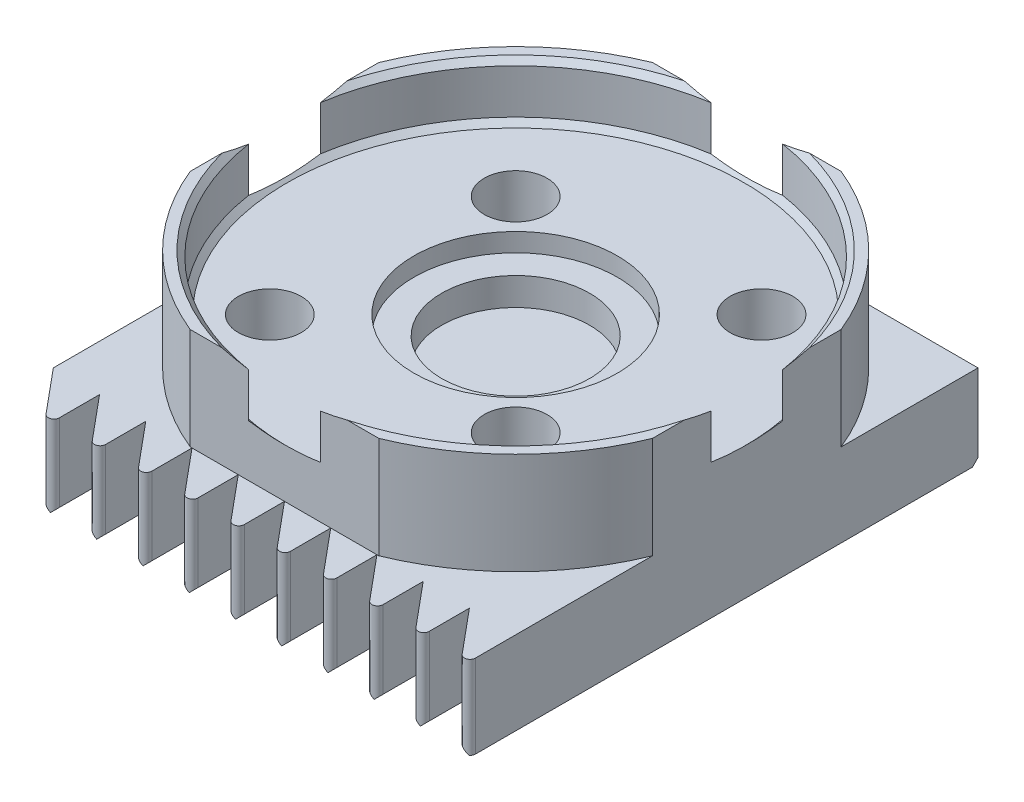
SolidWorks part; units mm, degrees
ref_plane "Front Plane" through (0, 0, 0) normal (0, 0, 1) x (1, 0, 0)
ref_plane "Top Plane" through (0, 0, 0) normal (0, 1, 0) x (1, 0, 0)
ref_plane "Right Plane" through (0, 0, 0) normal (1, 0, 0) x (0, 0, -1)
sketch "Sketch1" plane through (0, 0, 0) normal (0, 1, 0) x (1, 0, 0)
  line L0 (-6.6468, -6.6468) -> (6.6468, 6.6468) construction
  line L1 (-5.5331, 5.5331) -> (5.5331, -5.5331) construction
  line L2 (0, 0) -> (0, 3.1277) construction
  circle A0 centre (0, 0) radius 13.5
  circle A1 centre (0, 0) radius 5.5
  circle A2 centre (0, 0) radius 7.825 construction
  circle A3 centre (-5.5331, 5.5331) radius 1.7
  circle A4 centre (5.5331, -5.5331) radius 1.7
  circle A5 centre (0, 0) radius 9.4 construction
  circle A6 centre (-6.6468, -6.6468) radius 1.7
  circle A7 centre (6.6468, 6.6468) radius 1.7
  dimension "D1" = 27
  dimension "D2" = 11
  dimension "D3" = 15.65
  dimension "D4" = 18.8
  dimension "D5" = 3.4
  dimension "D6" = 45
extrude "Boss-Extrude1" add sketch "Sketch1" along normal blind 2.5 contours A0 A7 A6 A4 A3 A1 region at (-13.1182, 0, 0)
sketch "Sketch2" plane through (0, 2.5, 0) normal (0, 1, 0) x (1, 0, 0)
  circle A0 centre (0, 0) radius 12.65
  circle M6 centre (0, 0) radius 13.5
extrude "Boss-Extrude2" add sketch "Sketch2" along normal blind 3 contours A0 M6 region at (-13.1182, 2.5, 0)
sketch "Sketch3" plane through (0, 0, 0) normal (0, -1, 0) x (1, 0, 0)
  line L1 (12.5, -12.5) -> (-12.5, -12.5)
  line L2 (12.5, -12.5) -> (12.5, 12.5)
  line L3 (12.5, 12.5) -> (-12.5, 12.5)
  line L4 (-12.5, -12.5) -> (-12.5, 12.5)
  line L5 (12.5, -12.5) -> (-12.5, 12.5) construction
  line L6 (12.5, 12.5) -> (-12.5, -12.5) construction
  circle A0 centre (-5.5331, -5.5331) radius 1.7 construction
  circle A1 centre (6.6468, -6.6468) radius 1.7 construction
  circle A2 centre (5.5331, 5.5331) radius 1.7 construction
  circle A3 centre (-6.6468, 6.6468) radius 1.7 construction
  circle A4 centre (-5.5331, -5.5331) radius 1.7 construction
  circle A5 centre (6.6468, -6.6468) radius 1.7 construction
  circle A6 centre (5.5331, 5.5331) radius 1.7 construction
  circle A7 centre (-6.6468, 6.6468) radius 1.7 construction
  circle A8 centre (-6.6468, 6.6468) radius 3
  circle A9 centre (5.5331, 5.5331) radius 3
  circle A10 centre (6.6468, -6.6468) radius 3
  circle A11 centre (-5.5331, -5.5331) radius 3
  point P0 (0, 0)
  circle M5 centre (0, 0) radius 5.5
  circle M6 centre (0, 0) radius 13.5
  dimension "D1" = 6
  dimension "D2" = 25
extrude "Boss-Extrude3" add sketch "Sketch3" along normal blind 4.5 contours L4 L1 L2 L3 A11 A9 A10 A8 M6 M5 | L4 L3 M6 | L4 L1 M6 | L1 L2 M6 | L2 L3 M6 | A11 A9 M5 region at (10.3804, 0, -10.3804) region at (0, 0, -12.1464) region at (-10.3804, 0, -10.3804) region at (10.3804, 0, 10.3804) region at (-10.3804, 0, 10.3804) region at (0, 0, 0)
chamfer "Chamfer2" distance 0.3 angle 45 1 edges at (0, 2.5, 12.65)
sketch "Sketch4" plane through (0, 0, 0) normal (0, 1, 0) x (1, 0, 0)
  circle A0 centre (0, 0) radius 5.5 construction
  circle A1 centre (0, 0) radius 5.5
  circle A2 centre (0, 0) radius 4
  arc M1 (2.6146, -4.8388) -> (4.8388, -2.6146) centre (5.5331, -5.5331) cw
  arc M2 (4.8388, -2.6146) -> (-2.6146, 4.8388) centre (0, 0) ccw
  arc M3 (-2.6146, 4.8388) -> (-4.8388, 2.6146) centre (-5.5331, 5.5331) cw
  arc M4 (-4.8388, 2.6146) -> (2.6146, -4.8388) centre (0, 0) ccw
  dimension "D1" = 8
extrude "Boss-Extrude4" add sketch "Sketch4" along normal blind 1.5 contours A2 M4 M1 M2 M3 | A1 M3 | A1 M1 region at (5.1813, 0, 1.3103) region at (-3.6647, 0, -3.6647) region at (3.6647, 0, 3.6647)
sketch "Sketch6" plane through (0, 0, 0) normal (0, -1, 0) x (1, 0, 0)
  line L0 (5.099, -12.5) -> (-5.099, -12.5) construction
  line L1 (12.5, 5.099) -> (12.5, -5.099) construction
  line L2 (-5.099, 12.5) -> (5.099, 12.5) construction
  line L3 (-12.5, -5.099) -> (-12.5, 5.099) construction
  line L4 (5.099, -12.5) -> (-5.099, -12.5)
  line L5 (12.5, 5.099) -> (12.5, -5.099)
  line L6 (-5.099, 12.5) -> (5.099, 12.5)
  line L7 (-12.5, -5.099) -> (-12.5, 5.099)
  arc A0 (-5.099, -12.5) -> (5.099, -12.5) centre (0, 0) ccw construction
  arc A1 (12.5, -5.099) -> (12.5, 5.099) centre (0, 0) ccw construction
  arc A2 (5.099, 12.5) -> (-5.099, 12.5) centre (0, 0) ccw construction
  arc A3 (-12.5, 5.099) -> (-12.5, -5.099) centre (0, 0) ccw construction
  arc A4 (-5.099, -12.5) -> (5.099, -12.5) centre (0, 0) ccw
  arc A5 (12.5, -5.099) -> (12.5, 5.099) centre (0, 0) ccw
  arc A6 (5.099, 12.5) -> (-5.099, 12.5) centre (0, 0) ccw
  arc A7 (-12.5, 5.099) -> (-12.5, -5.099) centre (0, 0) ccw
extrude "Cut-Extrude1" cut sketch "Sketch6" against normal through all
chamfer "Chamfer3" distance 0.3 angle 45 4 edges at (8.9449, 5.5, -8.9449) (-8.9449, 5.5, -8.9449) (-8.9449, 5.5, 8.9449) (8.9449, 5.5, 8.9449)
sketch "Sketch7" plane through (0, -4.5, 0) normal (0, -1, 0) x (1, 0, 0)
  line L0 (12.5, 12.5) -> (-12.5, 12.5) construction
  line L1 (12.5, 12.5) -> (-12.5, 12.5)
  line L2 (-12.5, 12.5) -> (-10, 15.5)
  line L3 (-10, 15.5) -> (-10, 12.5)
  line L4 (-7.5, 15.5) -> (-7.5, 12.5)
  line L5 (-10, 12.5) -> (-7.5, 15.5)
  line L6 (-5, 15.5) -> (-5, 12.5)
  line L7 (-7.5, 12.5) -> (-5, 15.5)
  line L8 (-2.5, 15.5) -> (-2.5, 12.5)
  line L9 (-5, 12.5) -> (-2.5, 15.5)
  line L10 (0, 15.5) -> (0, 12.5)
  line L11 (-2.5, 12.5) -> (0, 15.5)
  line L12 (2.5, 15.5) -> (2.5, 12.5)
  line L13 (0, 12.5) -> (2.5, 15.5)
  line L14 (5, 15.5) -> (5, 12.5)
  line L15 (2.5, 12.5) -> (5, 15.5)
  line L16 (7.5, 15.5) -> (7.5, 12.5)
  line L17 (5, 12.5) -> (7.5, 15.5)
  line L18 (10, 15.5) -> (10, 12.5)
  line L19 (7.5, 12.5) -> (10, 15.5)
  line L20 (12.5, 15.5) -> (12.5, 12.5)
  line L21 (10, 12.5) -> (12.5, 15.5)
  line M9 (12.5, 12.5) -> (-12.5, 12.5)
  dimension "D1" = 3
  dimension "D2" = 2.5
  dimension "D3" = 10
extrude "Boss-Extrude5" add sketch "Sketch7" against normal up to surface (4.5 mm away) contours L3 L2 L1 | L5 L1 L4 | L7 L1 L6 | L9 L1 L8 | L11 L1 L10 | L13 L1 L12 | L15 L1 L14 | L17 L1 L16 | L19 L1 L18 | L21 L20 M9 region at (-10.8333, -4.5, 13.5) region at (-8.3333, -4.5, 13.5) region at (-5.8333, -4.5, 13.5) region at (-3.3333, -4.5, 13.5) region at (-0.8333, -4.5, 13.5) region at (1.6667, -4.5, 13.5) region at (4.1667, -4.5, 13.5) region at (6.6667, -4.5, 13.5) region at (9.1667, -4.5, 13.5) region at (11.6667, -4.5, 13.5) up to face at (5.5331, 0, 7.2331)
chamfer "Chamfer4" distance 0.3 angle 45 20 edges at (0, -4.5, -12.5) (11.25, -4.5, 14) (10, -4.5, 14) (8.75, -4.5, 14) (7.5, -4.5, 14) (6.25, -4.5, 14) (5, -4.5, 14) (3.75, -4.5, 14) (2.5, -4.5, 14) (1.25, -4.5, 14) (0, -4.5, 14) (-1.25, -4.5, 14) (-2.5, -4.5, 14) (-3.75, -4.5, 14) (-5, -4.5, 14) (-6.25, -4.5, 14) (-7.5, -4.5, 14) (-8.75, -4.5, 14) (-10, -4.5, 14) (-11.25, -4.5, 14)
fillet "Fillet1" radius 0.3 10 edges at (10, -2.1, 15.5) (7.5, -2.1, 15.5) (5, -2.1, 15.5) (2.5, -2.1, 15.5) (0, -2.1, 15.5) (-2.5, -2.1, 15.5) (-5, -2.1, 15.5) (-7.5, -2.1, 15.5) (-10, -2.1, 15.5) (12.5, -2.1, 15.5)
sketch "Sketch8" plane through (0, -4.5, 0) normal (0, -1, 0) x (1, 0, 0)
  circle A0 centre (0, 0) radius 1.5
  point P2 (0, 0)
  dimension "D2" = 3
extrude "Cut-Extrude2" cut sketch "Sketch8" against normal blind 3
chamfer "Chamfer5" distance 2 angle 45 4 edges at (6.6468, 0, -9.6468) (-5.5331, 0, -8.5331) (5.5331, 0, 2.5331) (-6.6468, 0, 3.6468)
